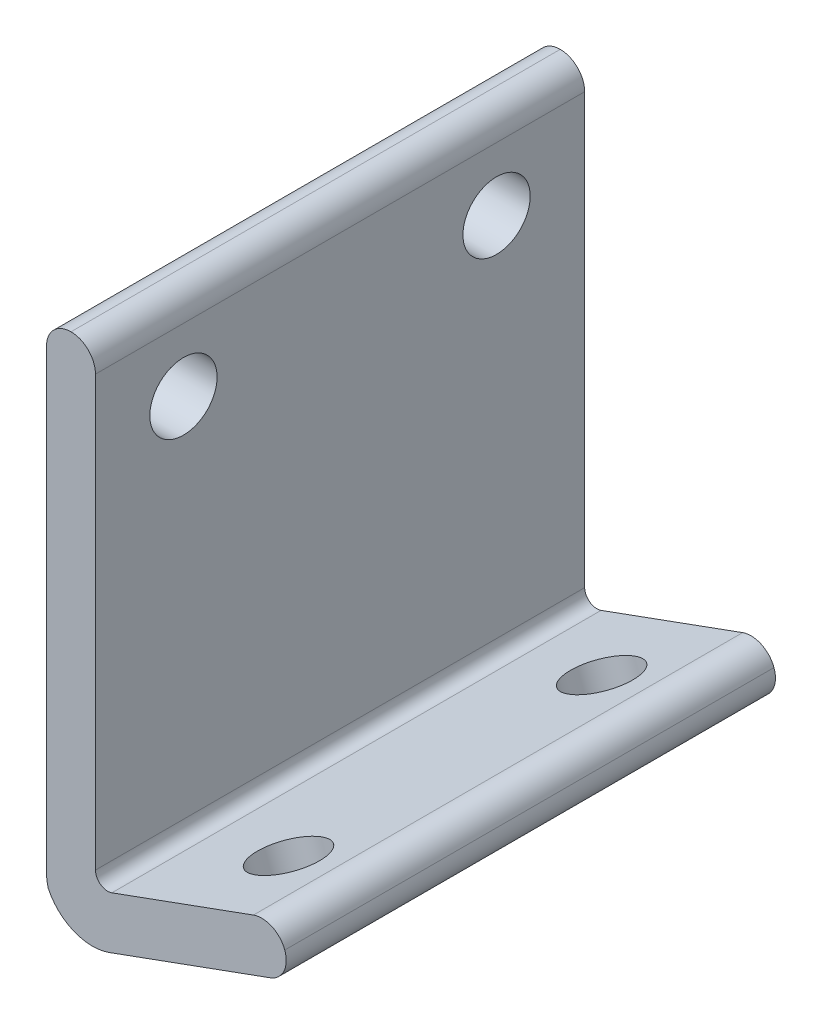
SolidWorks part; units mm, degrees
ref_plane "Front Plane" through (0, 0, 0) normal (0, 0, 1) x (1, 0, 0)
ref_plane "Top Plane" through (0, 0, 0) normal (0, 1, 0) x (1, 0, 0)
ref_plane "Right Plane" through (0, 0, 0) normal (1, 0, 0) x (0, 0, -1)
sketch "Sketch1" plane through (0, 0, 0) normal (1, 0, 0) x (0, 0, -1)
  line L0 (0, 53.7012) -> (0, 0) construction
  line L1 (0, 0) -> (120.6769, 0) construction
ref_plane "Plane1" through (0, 0, 0) normal (0.342, -0.9397, 0) x (0, 0, -1)
sketch "Sketch2" plane through (0, 0, 0) normal (1, 0, 0) x (0, 0, -1)
  line L0 (0, 0) -> (0, 20)
  line L1 (0, 53.7012) -> (0, 0) construction
  line L2 (0, 20) -> (20, 20)
  line L3 (20, 20) -> (20, 0)
  line L4 (0, 0) -> (120.6769, 0) construction
  line L5 (20, 0) -> (0, 0)
  line L6 (10, 20) -> (10, 0) construction
  circle A0 centre (3.5971, 16.4156) radius 1.375
  circle A1 centre (16.3971, 16.4156) radius 1.375
  point P16 (10, 10)
  dimension "D4" = 2.75
  dimension "D5" = 2.75
  dimension "D1" = 20
  dimension "D2" = 20
  dimension "D3" = 12.8
sketch "Sketch3" plane through (0, 0, 0) normal (0.342, -0.9397, 0) x (0, 0, -1)
  line L0 (0, 0) -> (0, 10)
  line L1 (0, 18.3669) -> (0, 0) construction
  line L2 (0, 10) -> (20, 10)
  line L3 (20, 10) -> (20, 0)
  line L4 (0, 0) -> (120.6769, 0) construction
  line L5 (20, 0) -> (0, 0)
  line L6 (10, 10) -> (10, 0) construction
  circle A0 centre (3.6, 6.6963) radius 1.35
  circle A1 centre (16.4, 6.6963) radius 1.35
  point P16 (10, 5)
  dimension "D4" = 2.7
  dimension "D5" = 2.7
  dimension "D1" = 20
  dimension "D2" = 10
  dimension "D3" = 12.8
extrude "Boss-Extrude1" add sketch "Sketch3" along normal blind 2
extrude "Boss-Extrude2" add sketch "Sketch2" along normal blind 2
fillet "Fillet1" radius 2 2 edges at (0.684, -1.8794, -10) (0, 0, -10)
fillet "Fillet2" radius 0.5 1 edges at (2, 0.7279, -10)
fillet "Fillet3" radius 1 2 edges at (2, 20, -10) (0, 20, -10)
fillet "Fillet4" radius 1 2 edges at (10.081, 1.5408, -10) (9.3969, 3.4202, -10)
